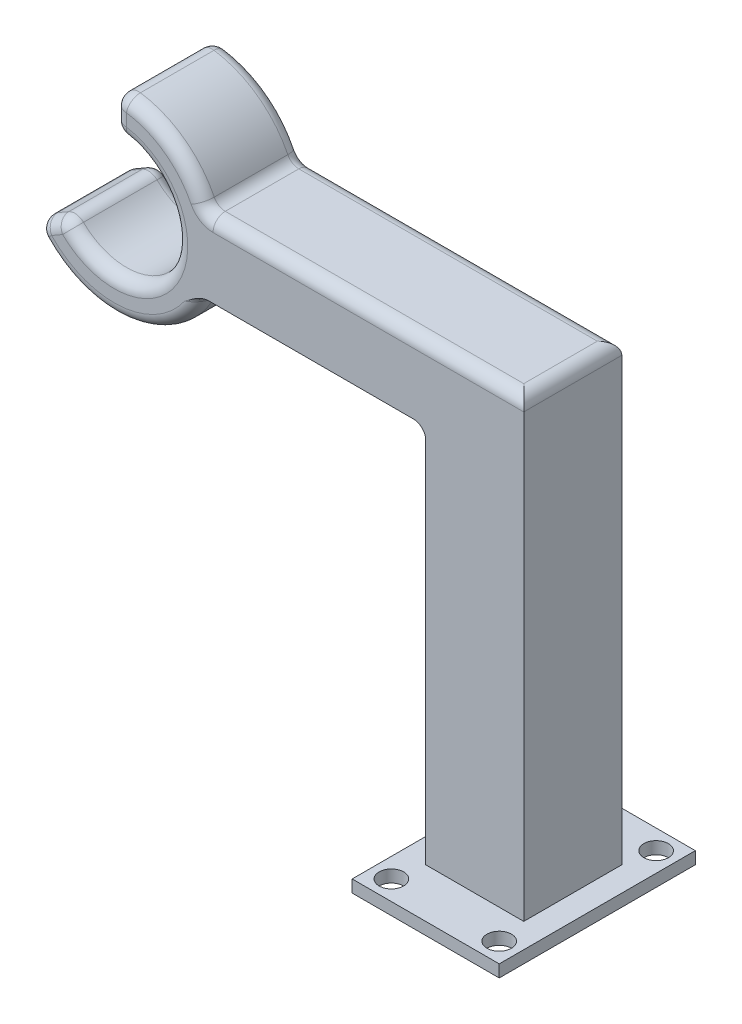
SolidWorks part; units mm, degrees
material "Cast Carbon Steel"
ref_plane "Front Plane" through (0, 0, 0) normal (0, 0, 1) x (1, 0, 0)
ref_plane "Top Plane" through (0, 0, 0) normal (0, 1, 0) x (1, 0, 0)
ref_plane "Right Plane" through (0, 0, 0) normal (1, 0, 0) x (0, 0, -1)
sketch "Sketch1" plane through (0, 0, 0) normal (0, 0, 1) x (1, 0, 0)
  line L0 (0, 31.75) -> (0, 50.8)
  line L1 (-25.4, -19.05) -> (-41.9721, -28.6179)
  arc A0 (-41.9721, -28.6179) -> (0, 50.8) centre (0, 0) ccw
  arc A1 (-25.4, -19.05) -> (0, 31.75) centre (0, 0) ccw
  dimension "D1" = 101.6
  dimension "D2" = 63.5
  dimension "D3" = 120
  dimension "D4" = 25.4
extrude "Boss-Extrude1" add sketch "Sketch1" along normal blind 50.8
sketch "Sketch2" plane through (0, 0, 0) normal (0, 0, 1) x (1, 0, 0)
  line L0 (212.1929, 19.05) -> (212.1929, -19.05)
  line L1 (47.0929, -19.05) -> (212.1929, -19.05)
  line L2 (47.0929, 19.05) -> (212.1929, 19.05)
  arc A0 (-41.9721, -28.6179) -> (0, 50.8) centre (0, 0) ccw construction
  arc A1 (47.0929, -19.05) -> (47.0929, 19.05) centre (0, 0) ccw
  point P0 (50.8, 0)
  dimension "D3" = 50.8
  dimension "D1" = 38.1
  dimension "D2" = 165.1
extrude "Boss-Extrude2" add sketch "Sketch2" along normal blind 50.8
fillet "Fillet2" radius 6.35 18 edges at (28.3981, 42.1211, 50.8) (28.3981, 42.1211, 0) (0, 50.8, 25.4) (0, 41.275, 50.8) (0, 41.275, 0) (-33.686, -23.8339, 50.8) (-41.9721, -28.6179, 25.4) (-33.686, -23.8339, 0) (212.1929, 19.05, 25.4) (129.6429, 19.05, 50.8) (47.0929, 19.05, 25.4) (129.6429, 19.05, 0) (0, 31.75, 25.4) (28.3981, -14.199, 50.8) (-25.4, -19.05, 25.4) (28.3981, -14.199, 0) (5.426, -50.5094, 0) (5.426, -50.5094, 50.8)
sketch "Sketch4" plane through (0, -19.05, 0) normal (0, -1, 0) x (1, 0, 0)
  line L1 (212.1929, 50.8) -> (161.3929, 50.8)
  line L2 (212.1929, 50.8) -> (212.1929, 0)
  line L3 (212.1929, 0) -> (161.3929, 0)
  line L4 (161.3929, 50.8) -> (161.3929, 0)
  dimension "D1" = 50.8
extrude "Boss-Extrude4" add sketch "Sketch4" along normal blind 196.85
fillet "Fillet3" radius 6.35 4 edges at (44.8402, -19.05, 49.1508) (45.7739, -19.05, 2.6073) (47.0929, -19.05, 25.4) (161.3929, -19.05, 25.4)
sketch "Sketch5" plane through (0, -215.9, 0) normal (0, -1, 0) x (1, 0, 0)
  line L0 (161.3929, 50.8) -> (161.3929, 0) construction
  line L1 (224.8929, 76.2) -> (148.6929, 76.2)
  line L2 (224.8929, 76.2) -> (224.8929, -25.4)
  line L3 (224.8929, -25.4) -> (148.6929, -25.4)
  line L4 (148.6929, 76.2) -> (148.6929, -25.4)
  line L5 (224.8929, 76.2) -> (148.6929, -25.4) construction
  line L6 (224.8929, -25.4) -> (148.6929, 76.2) construction
  line L7 (161.3929, 0) -> (212.1929, 0) construction
  point P0 (186.7929, 25.4)
  point P8 (161.3929, 25.4)
  point P12 (186.7929, 0)
  dimension "D1" = 76.2
  dimension "D2" = 101.6
extrude "Boss-Extrude5" add sketch "Sketch5" along normal blind 6.35
sketch "Sketch6" plane through (0, -215.9, 0) normal (0, 1, 0) x (1, 0, 0)
  line L0 (148.6929, -76.2) -> (148.6929, 25.4) construction
  line L1 (224.8929, -76.2) -> (148.6929, -76.2) construction
  circle A0 centre (158.8529, -66.04) radius 6.35
  dimension "D3" = 12.7
  dimension "D1" = 10.16
  dimension "D2" = 10.16
extrude "Cut-Extrude1" cut sketch "Sketch6" against normal through all
sketch "Sketch7" plane through (0, -215.9, 0) normal (0, 1, 0) x (1, 0, 0)
  line L0 (224.8929, -76.2) -> (148.6929, -76.2) construction
  line L1 (224.8929, 25.4) -> (224.8929, -76.2) construction
  line L2 (148.6929, 25.4) -> (224.8929, 25.4) construction
  line L3 (148.6929, -76.2) -> (148.6929, 25.4) construction
  circle A0 centre (214.7329, -66.04) radius 6.35
  circle A1 centre (214.7329, 15.24) radius 6.35
  circle A2 centre (158.8529, 15.24) radius 6.731
  dimension "D1" = 13.462
  dimension "D2" = 12.7
  dimension "D3" = 12.7
  dimension "D4" = 10.16
  dimension "D5" = 10.16
  dimension "D6" = 10.16
  dimension "D7" = 10.16
  dimension "D8" = 10.16
  dimension "D9" = 10.16
extrude "Cut-Extrude2" cut sketch "Sketch7" against normal through all
